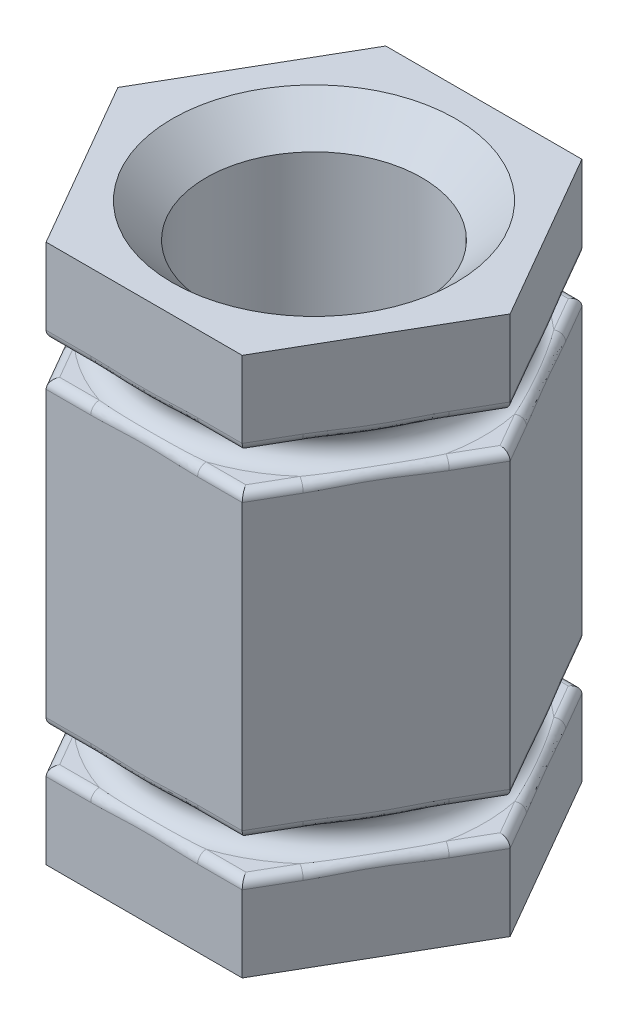
SolidWorks part; units mm, degrees
ref_plane "Front Plane" through (0, 0, 0) normal (0, 0, 1) x (1, 0, 0)
ref_plane "Top Plane" through (0, 0, 0) normal (0, 1, 0) x (1, 0, 0)
ref_plane "Right Plane" through (0, 0, 0) normal (1, 0, 0) x (0, 0, -1)
sketch "Sketch1" plane through (0, 0, 0) normal (0, 1, 0) x (1, 0, 0)
  line L5 (-5.7735, 0) -> (-2.8868, -5)
  line L6 (-2.8868, -5) -> (2.8868, -5)
  line L7 (2.8868, -5) -> (5.7735, 0)
  line L8 (5.7735, 0) -> (2.8868, 5)
  line L9 (2.8868, 5) -> (-2.8868, 5)
  line L10 (-2.8868, 5) -> (-5.7735, 0)
  circle A0 centre (0, 0) radius 3.175
  circle A2 centre (0, 0) radius 5 construction
  point P3 (0, 0)
  dimension "D1" = 6.35
  dimension "D2" = 10
extrude "Boss-Extrude1" add sketch "Sketch1" along normal blind 15.875
sketch "Sketch2" plane through (0, 0, 0) normal (0, 0, 1) x (1, 0, 0)
  line L3 (0, 15.875) -> (0, 0) construction
  line L4 (-2.8868, 15.875) -> (-5.7735, 15.875) construction
  line L5 (-2.8868, 0) -> (-5.7735, 0) construction
  line L6 (-5, 13.375) -> (-6.7735, 13.375)
  line L7 (-6.7735, 13.375) -> (-6.7735, 12.375)
  line L8 (-6.7735, 12.375) -> (-5, 12.375)
  line L9 (-5.7735, 15.875) -> (-5.7735, 0) construction
  line L10 (-5, 3.5) -> (-6.7735, 3.5)
  line L11 (-6.7735, 3.5) -> (-6.7735, 2.5)
  line L12 (-6.7735, 2.5) -> (-5, 2.5)
  line L13 (2.8868, 15.875) -> (-2.8868, 15.875) construction
  arc A0 (-5, 12.375) -> (-5, 13.375) centre (-5, 12.875) ccw
  arc A1 (-5, 2.5) -> (-5, 3.5) centre (-5, 3) ccw
  point P5 (0, 0)
  point P9 (0, 0)
  dimension "D1" = 1
  dimension "D2" = 10
  dimension "D3" = 3
  dimension "D4" = 3
  dimension "D5" = 1
revolve "Cut-Revolve1" cut sketch "Sketch2" angle 360 about L3
fillet "Fillet1" radius 0.254 48 edges at (5.0518, 2.5, -1.25) (1.4434, 2.5, -5) (-5.0518, 2.5, -1.25) (-3.6084, 2.5, 3.75) (5.0518, 2.5, 1.25) (1.4434, 2.5, 5) (-3.6084, 3.5, 3.75) (-1.4434, 3.5, 5) (5.0518, 3.5, 1.25) (5.0518, 3.5, -1.25) (1.4434, 3.5, -5) (-5.0518, 3.5, -1.25) (-5.0518, 13.375, -1.25) (-1.4434, 13.375, -5) (3.6084, 13.375, -3.75) (5.0518, 13.375, 1.25) (1.4434, 13.375, 5) (-5.0518, 13.375, 1.25) (-5.0518, 12.375, 1.25) (-1.4434, 12.375, 5) (3.6084, 12.375, 3.75) (5.0518, 12.375, -1.25) (1.4434, 12.375, -5) (-3.6084, 12.375, -3.75) (3.6084, 2.5, -3.75) (-1.4434, 2.5, -5) (-3.6084, 2.5, -3.75) (-5.0518, 2.5, 1.25) (3.6084, 2.5, 3.75) (-1.4434, 2.5, 5) (-5.0518, 3.5, 1.25) (1.4434, 3.5, 5) (3.6084, 3.5, 3.75) (3.6084, 3.5, -3.75) (-1.4434, 3.5, -5) (-3.6084, 3.5, -3.75) (-3.6084, 13.375, -3.75) (1.4434, 13.375, -5) (5.0518, 13.375, -1.25) (3.6084, 13.375, 3.75) (-1.4434, 13.375, 5) (-3.6084, 13.375, 3.75) (-3.6084, 12.375, 3.75) (1.4434, 12.375, 5) (5.0518, 12.375, 1.25) (3.6084, 12.375, -3.75) (-1.4434, 12.375, -5) (-5.0518, 12.375, -1.25)
sketch "Sketch3" plane through (0, 0, 0) normal (0, 0, 1) x (1, 0, 0)
  line L1 (-2.8868, 15.875) -> (2.8868, 15.875) construction
  circle A0 centre (0, 9.875) radius 1.025
  point P2 (0, 0)
  point P4 (0, 0)
  dimension "D1" = 2.05
  dimension "D2" = 6
extrude "Cut-Extrude1" cut sketch "Sketch3" against normal blind 10
chamfer "Chamfer1" distance 1 angle 45 2 edges at (0, 0, 3.175) (0, 15.875, 3.175)
chamfer "Chamfer2" distance 0.25 angle 45 1 edges at (1.025, 9.875, -5)
ref_plane "Plane1" through (0, 12.875, 0) normal (0, 1, 0) x (1, 0, 0)
ref_plane "Plane2" through (0, 3, 0) normal (0, 1, 0) x (1, 0, 0)
sketch "Sketch6" plane through (0, 3, 0) normal (0, 1, 0) x (1, 0, 0)
  circle A0 centre (0, 0) radius 5
  dimension "D1" = 10
sketch "Sketch7" plane through (0, 12.875, 0) normal (0, 1, 0) x (1, 0, 0)
  circle A0 centre (0, 0) radius 5 construction
  circle A1 centre (0, 0) radius 5
